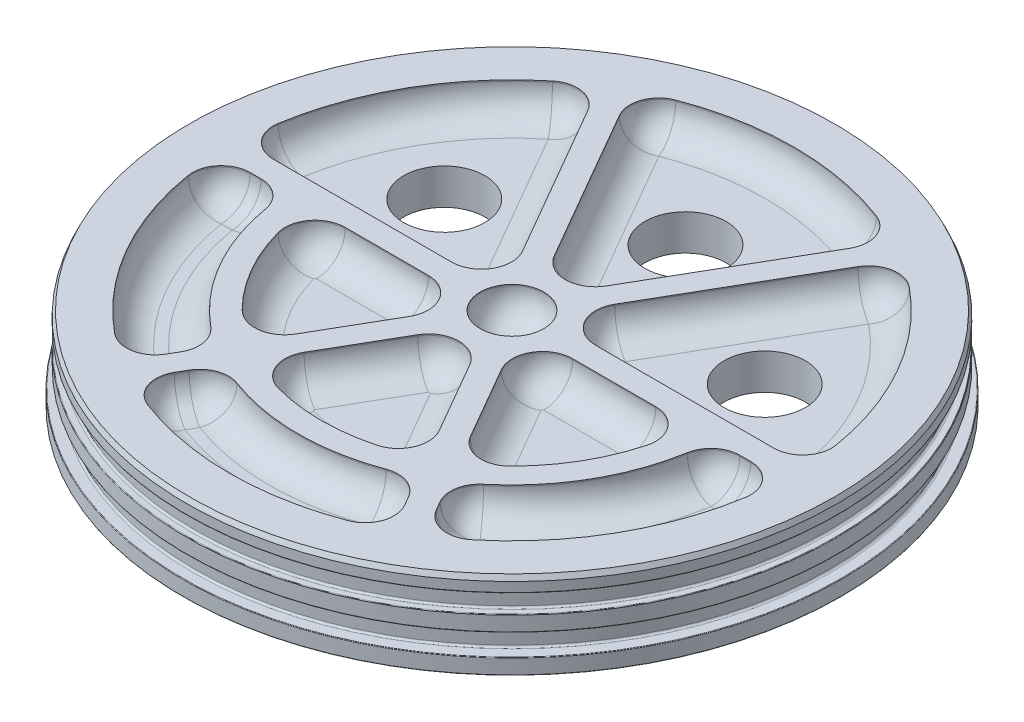
SolidWorks part; units mm, degrees
material "6061-T6 (SS)"
ref_plane "Front Plane" through (0, 0, 0) normal (0, 0, 1) x (1, 0, 0)
ref_plane "Top Plane" through (0, 0, 0) normal (0, 1, 0) x (1, 0, 0)
ref_plane "Right Plane" through (0, 0, 0) normal (1, 0, 0) x (0, 0, -1)
sketch "Sketch1" plane through (0, 0, 0) normal (0, 0, 1) x (1, 0, 0)
  line L0 (0, 48.1922) -> (0, -25.6743) construction
  line L1 (0, 0) -> (72.39, 0)
  line L2 (72.39, 0) -> (72.39, 3.429)
  line L3 (72.39, 3.429) -> (69.6468, 3.429)
  line L4 (69.6468, 3.429) -> (69.6468, 7.493)
  line L5 (69.6468, 7.493) -> (71.4248, 7.493)
  line L6 (71.4248, 7.493) -> (71.4248, 10.922)
  line L7 (71.4248, 10.922) -> (69.6468, 10.922)
  line L8 (62.0268, 18.288) -> (62.0268, 11.684)
  line L9 (62.0268, 11.684) -> (0, 11.684)
  line L10 (0, 11.684) -> (0, 0)
  line L11 (69.6468, 10.922) -> (69.6468, 14.986)
  line L12 (69.6468, 14.986) -> (71.4248, 14.986)
  line L13 (71.4248, 14.986) -> (71.4248, 18.288)
  line L14 (71.4248, 18.288) -> (62.0268, 18.288)
  dimension "D2" = 4.064
  dimension "D5" = 11.684
  dimension "D7" = 4.064
  dimension "D3" = 3.302
  dimension "D4" = 3.429
  dimension "D8" = 7.62
  dimension "D9" = 6.604
  dimension "D1" = 72.39
  dimension "D10" = 1.778
  dimension "D6" = 69.6468
revolve "Revolve1" add sketch "Sketch1" angle 360 about L0
sketch "Sketch6" plane through (0, 0, 0) normal (0, -1, 0) x (1, 0, 0)
  circle A0 centre (0, 0) radius 66.04
  dimension "D1" = 132.08
extrude "Boss-Extrude1" add sketch "Sketch6" along normal blind 2.54
fillet "CNC ID Fillet" radius 0.4064 5 edges at (-69.6468, 7.493, 0) (-69.6468, 3.429, 0) (66.04, 0, 0) (-69.6468, 14.986, 0) (-69.6468, 10.922, 0)
fillet "CNC OD Fillet" radius 0.127 6 edges at (-71.4248, 7.493, 0) (-72.39, 3.429, 0) (-71.4248, 10.922, 0) (-71.4248, 14.986, 0) (66.04, -2.54, 0) (-72.39, 0, 0)
chamfer "CNC Chamfers" distance 0.508 angle 65 1 edges at (-71.4248, 18.288, 0) first distance on face at (-62.0268, 18.288, 0)
hole_wizard "Pipe Tap Drill for 1/2 Tap - Fill Valve" positions "Sketch13" profile "Sketch14" hole size "1/2" standard "ANSI Inch" end condition through all
sketch "Sketch13" plane through (0, -2.54, 0) normal (0, -1, 0) x (-1, 0, 0)
  point P4 (0, 38.1)
  dimension "D1" = 38.1
sketch "Sketch14" plane through (0, -2.54, -38.1) normal (1, 0, 0) x (0, 0, -1)
  line L0 (0, 0) -> (0, 20.828)
  line L1 (0, 20.828) -> (8.9281, 20.828)
  line L2 (8.9281, 20.828) -> (8.9281, 0)
  line L5 (8.9281, 0) -> (0, 0)
  line L11 (0, -6.35) -> (0, 107.95) construction
  dimension "Thru Hole Dia." = 17.8562
  dimension "Thru Hole Depth" = 20.828
hole_wizard "Pipe Tap Drill for 1/4 Tap - Solenoid Valve" positions "Sketch15" profile "Sketch16" hole size "1/2" standard "ANSI Inch" end condition through all
sketch "Sketch15" plane through (0, -2.54, 0) normal (0, -1, 0) x (-1, 0, 0)
  line L2 (-35.1953, 20.32) -> (0, 0) construction
  line L4 (0, 0) -> (0, 38.1) construction
  point P4 (-35.1953, 20.32)
  dimension "D1" = 60
  dimension "D2" = 40.64
sketch "Sketch16" plane through (35.1953, -2.54, -20.32) normal (1, 0, 0) x (0, 0, -1)
  line L0 (0, 0) -> (0, 20.828)
  line L1 (0, 20.828) -> (8.9281, 20.828)
  line L2 (8.9281, 20.828) -> (8.9281, 0)
  line L5 (8.9281, 0) -> (0, 0)
  line L11 (0, -6.35) -> (0, 107.95) construction
  dimension "Thru Hole Dia." = 17.8562
  dimension "Thru Hole Depth" = 20.828
hole_wizard "Pipe Tap Drill for 1/2 Tap - Cryo Valve" positions "Sketch17" profile "Sketch18" hole size "1/2" standard "ANSI Inch" end condition through all
sketch "Sketch17" plane through (0, -2.54, 0) normal (0, -1, 0) x (-1, 0, 0)
  line L2 (35.1953, 20.32) -> (0, 0) construction
  line L5 (0, 0) -> (0, 38.1) construction
  point P4 (35.1953, 20.32)
  dimension "D1" = 60
  dimension "D2" = 40.64
sketch "Sketch18" plane through (-35.1953, -2.54, -20.32) normal (1, 0, 0) x (0, 0, -1)
  line L0 (0, 0) -> (0, 20.828)
  line L1 (0, 20.828) -> (8.9281, 20.828)
  line L2 (8.9281, 20.828) -> (8.9281, 0)
  line L5 (8.9281, 0) -> (0, 0)
  line L11 (0, -6.35) -> (0, 107.95) construction
  dimension "Thru Hole Dia." = 17.8562
  dimension "Thru Hole Depth" = 20.828
sketch "Sketch19" plane through (0, 18.288, 0) normal (0, 1, 0) x (1, 0, 0)
  line L0 (0, 0) -> (31.0134, 53.7168) construction
  line L1 (0, 0) -> (-31.0134, 53.7168) construction
  line L2 (0, 0) -> (62.0268, 0) construction
  line L3 (0, 0) -> (0, 38.1) construction
  line L4 (0, 0) -> (31.0134, -53.7168) construction
  line L5 (0, 0) -> (-31.0134, -53.7168) construction
  line L6 (0, 0) -> (-62.0268, 0) construction
  line L7 (-5.7192, 14.986) -> (-28.8137, 54.9868)
  line L8 (-15.8379, 2.54) -> (-62.0268, 2.54)
  line L9 (-10.1186, -12.446) -> (-19.2504, -28.2626)
  line L10 (5.7192, -14.986) -> (14.851, -30.8026)
  line L11 (15.8379, -2.54) -> (34.1013, -2.54)
  line L12 (10.1186, 12.446) -> (33.2131, 52.4468)
  line L13 (-10.1186, 12.446) -> (-33.2131, 52.4468)
  line L14 (-15.8379, -2.54) -> (-34.1013, -2.54)
  line L15 (-5.7192, -14.986) -> (-14.851, -30.8026)
  line L16 (10.1186, -12.446) -> (23.1162, -34.9584)
  line L17 (15.8379, 2.54) -> (62.0268, 2.54)
  line L18 (5.7192, 14.986) -> (28.8137, 54.9868)
  line L19 (0, -2.54) -> (-62.0268, -2.54) construction
  line L20 (-2.1997, 1.27) -> (-33.2131, -52.4468) construction
  line L21 (-2.1997, -1.27) -> (28.8137, -54.9868) construction
  line L22 (2.1997, -1.27) -> (-28.8137, -54.9868) construction
  line L23 (2.1997, 1.27) -> (33.2131, -52.4468) construction
  line L24 (0, -2.54) -> (62.0268, -2.54) construction
  line L25 (0, 2.54) -> (62.0268, 2.54) construction
  line L26 (2.1997, -1.27) -> (33.2131, 52.4468) construction
  line L27 (-2.1997, 1.27) -> (28.8137, 54.9868) construction
  line L28 (2.1997, 1.27) -> (-28.8137, 54.9868) construction
  line L29 (0, 2.54) -> (-62.0268, 2.54) construction
  line L30 (-2.1997, -1.27) -> (-33.2131, 52.4468) construction
  line L31 (-46.9213, -2.54) -> (-62.0268, -2.54)
  line L32 (46.9213, -2.54) -> (62.0268, -2.54)
  line L35 (-25.6604, -39.365) -> (-33.2131, -52.4468)
  line L36 (-21.2609, -41.905) -> (-28.8137, -54.9868)
  line L37 (21.2609, -41.905) -> (28.8137, -54.9868)
  line L38 (25.6604, -39.365) -> (33.2131, -52.4468)
  circle A0 centre (0, 0) radius 6.985
  circle A2 centre (0, 0) radius 62.0268
  arc A6 (-15.8379, -2.54) -> (-10.1186, -12.446) centre (-15.8379, -9.144) cw
  arc A7 (5.7192, -14.986) -> (-5.7192, -14.986) centre (0, -18.288) ccw
  arc A8 (10.1186, -12.446) -> (15.8379, -2.54) centre (15.8379, -9.144) cw
  arc A9 (15.8379, 2.54) -> (10.1186, 12.446) centre (15.8379, 9.144) cw
  arc A10 (5.7192, 14.986) -> (-5.7192, 14.986) centre (0, 18.288) cw
  arc A11 (-15.8379, 2.54) -> (-10.1186, 12.446) centre (-15.8379, 9.144) ccw
  arc A12 (-44.3774, -2.54) -> (44.3774, -2.54) centre (0, 0) ccw construction
  arc A13 (-46.9213, -2.54) -> (-25.6604, -39.365) centre (0, 0) ccw
  arc A14 (-40.48, -10.8544) -> (-29.6402, -29.6295) centre (0, 0) ccw
  arc A15 (-41.91, 0) -> (41.91, 0) centre (0, 0) ccw construction
  arc A16 (-44.45, 0) -> (44.45, 0) centre (0, 0) ccw construction
  arc A17 (-46.99, 0) -> (46.99, 0) centre (0, 0) ccw construction
  arc A19 (-10.8398, -40.4839) -> (10.8398, -40.4839) centre (0, 0) ccw
  arc A20 (23.1162, -34.9584) -> (40.48, -10.8544) centre (0, 0) ccw
  arc A21 (-21.2609, -41.905) -> (21.2609, -41.905) centre (0, 0) ccw
  arc A22 (25.6604, -39.365) -> (46.9213, -2.54) centre (0, 0) ccw
  arc A23 (-40.48, -10.8544) -> (-34.1013, -2.54) centre (-34.1013, -9.144) cw
  arc A24 (34.1013, -2.54) -> (40.48, -10.8544) centre (34.1013, -9.144) cw
  arc A25 (14.851, -30.8026) -> (10.8398, -40.4839) centre (9.1317, -34.1046) cw
  arc A26 (-10.8398, -40.4839) -> (-14.851, -30.8026) centre (-9.1317, -34.1046) cw
  arc A27 (-29.6402, -29.6295) -> (-19.2504, -28.2626) centre (-24.9696, -24.9606) ccw
  circle A28 centre (0, 0) radius 62.0268 construction
  point P12 (0, 0)
  point P13 (0, 0)
  dimension "D1" = 30
  dimension "D5" = 6.604
  dimension "D8" = 44.45
  dimension "D9" = 6.604
  dimension "D10" = 13.97
  dimension "D2" = 6
  dimension "D3" = 2.54
  dimension "D4" = 2.54
  dimension "D6" = 2.54
  dimension "D7" = 2.54
extrude "Boss-Extrude2" add sketch "Sketch19" against normal up to next contours A11 L8 L14 A6 L9 L15 A7 L10 L16 A8 L11 L17 A9 L12 L18 A10 L7 L13 region at (-0.1345, 18.288, 7.7292)
fillet "Fillet2" radius 6.35 61 edges at (-38.9063, 11.684, -2.54) (-10.1186, 11.684, -5.842) (-17.2535, 11.684, -34.9639) (0, 11.684, -11.684) (38.9063, 11.684, -2.54) (10.1186, 11.684, -5.842) (16.6174, 11.684, 23.7022) (10.1186, 11.684, 5.842) (24.9696, 11.684, 2.54) (-10.2851, 11.684, 22.8943) (0, 11.684, 11.684) (10.2851, 11.684, 22.8943) (-24.9696, 11.684, 2.54) (-10.1186, 11.684, 5.842) (-14.6845, 11.684, 20.3543) (-21.6529, 11.684, -32.4239) (17.2535, 11.684, -34.9639) (21.6529, 11.684, -32.4239) (34.0054, 11.684, 24.4965) (0, 11.684, 41.91) (-36.2951, 11.684, 20.955) (39.341, 11.684, 5.1242) (-15.2328, 11.684, 36.6324) (15.2328, 11.684, 36.6324) (-39.341, 11.684, 5.1242) (-24.1082, 11.684, 31.5082) (29.4237, 11.684, 45.8834) (40.6945, 11.684, 23.495) (54.448, 11.684, 2.54) (-25.0243, 11.684, 48.4234) (0, 11.684, 46.99) (25.0243, 11.684, 48.4234) (-54.448, 11.684, 2.54) (-40.6945, 11.684, 23.495) (-29.4237, 11.684, 45.8834) (46.9213, 14.986, 2.54) (25.6604, 14.986, 39.365) (21.2609, 14.986, 41.905) (-21.2609, 14.986, 41.905) (-25.6604, 14.986, 39.365) (-46.9213, 14.986, 2.54) (33.1871, 14.986, 52.4017) (61.9748, 14.986, 2.54) (-28.7877, 14.986, 54.9417) (28.7877, 14.986, 54.9417) (-61.9748, 14.986, 2.54) (-33.1871, 14.986, 52.4017) (-61.9748, 14.986, -2.54) (-33.1871, 14.986, -52.4017) (-28.7877, 14.986, -54.9417) (28.7877, 14.986, -54.9417) (61.9748, 14.986, -2.54) (33.1871, 14.986, -52.4017) (53.7168, 11.684, 31.0134) (0, 11.684, 62.0268) (-53.7168, 11.684, 31.0134) (-53.7168, 11.684, -31.0134) (53.7168, 11.684, -31.0134) (0, 11.684, -62.0268) (6.985, 11.684, 0) (23.1162, 14.986, 34.9584)
sketch "Sketch21" plane through (0, 18.288, 0) normal (0, 1, 0) x (1, 0, 0)
  circle A0 centre (0, 0) radius 66.3169 construction
  text T0 "                                                                                                                                                           RELEVANT EXPERIENCE"
sketch "Sketch22" plane through (0, -2.54, 0) normal (0, -1, 0) x (1, 0, 0)
  line L39 (-29.6809, -46.3289) -> (-10.1186, -12.446)
  line L59 (-15.8379, -2.54) -> (-54.9625, -2.54)
  line L74 (-29.6809, -46.3289) -> (-10.1186, -12.446)
  line L78 (-15.8379, -2.54) -> (-54.9625, -2.54)
  line L82 (-34.1013, 2.54) -> (-15.8379, 2.54)
  line L86 (-10.1186, 12.446) -> (-19.2504, 28.2626)
  line L90 (-34.1013, 2.54) -> (-15.8379, 2.54)
  line L94 (-10.1186, 12.446) -> (-19.2504, 28.2626)
  line L98 (15.8379, 2.54) -> (34.1013, 2.54)
  line L101 (19.4151, 28.548) -> (10.1186, 12.446)
  line L102 (15.8379, 2.54) -> (34.1013, 2.54)
  line L103 (19.4151, 28.548) -> (10.1186, 12.446)
  line L104 (-14.851, 30.8026) -> (-5.7192, 14.986)
  line L105 (5.7192, 14.986) -> (14.851, 30.8026)
  line L106 (-14.851, 30.8026) -> (-5.7192, 14.986)
  line L107 (5.7192, 14.986) -> (14.851, 30.8026)
  line L108 (-28.4967, 44.2777) -> (-29.6809, 46.3289)
  line L109 (-54.9625, 2.54) -> (-52.5939, 2.54)
  line L110 (-28.4967, 44.2777) -> (-29.6809, 46.3289)
  line L111 (-54.9625, 2.54) -> (-52.5939, 2.54)
  line L112 (24.0973, 46.8177) -> (25.2815, 48.8689)
  line L113 (-25.2815, 48.8689) -> (-24.0973, 46.8177)
  line L114 (24.0973, 46.8177) -> (25.2815, 48.8689)
  line L115 (-25.2815, 48.8689) -> (-24.0973, 46.8177)
  line L116 (52.5939, 2.54) -> (54.9625, 2.54)
  line L117 (29.6809, 46.3289) -> (28.4967, 44.2777)
  line L118 (52.5939, 2.54) -> (54.9625, 2.54)
  line L119 (29.6809, 46.3289) -> (28.4967, 44.2777)
  line L120 (10.1186, -12.446) -> (29.6809, -46.3289)
  line L121 (54.9625, -2.54) -> (15.8379, -2.54)
  line L122 (10.1186, -12.446) -> (29.6809, -46.3289)
  line L123 (54.9625, -2.54) -> (15.8379, -2.54)
  line L124 (-5.7192, -14.986) -> (-25.2815, -48.8689)
  line L125 (25.2815, -48.8689) -> (5.7192, -14.986)
  line L126 (-5.7192, -14.986) -> (-25.2815, -48.8689)
  line L127 (25.2815, -48.8689) -> (5.7192, -14.986)
  circle A3 centre (0, 0) radius 6.985
  circle A93 centre (0, 0) radius 6.985
  arc A205 (-61.231, -9.9039) -> (-39.1925, -48.0757) centre (0, 0) ccw
  arc A214 (-39.1925, -48.0757) -> (-29.6809, -46.3289) centre (-35.1802, -43.1539) ccw
  arc A217 (-10.1186, -12.446) -> (-15.8379, -2.54) centre (-15.8379, -9.144) ccw
  arc A229 (-54.9625, -2.54) -> (-61.231, -9.9039) centre (-54.9625, -8.89) ccw
  arc A241 (-61.231, -9.9039) -> (-39.1925, -48.0757) centre (0, 0) ccw
  arc A267 (-39.1925, -48.0757) -> (-29.6809, -46.3289) centre (-35.1802, -43.1539) ccw
  arc A268 (-10.1186, -12.446) -> (-15.8379, -2.54) centre (-15.8379, -9.144) ccw
  arc A269 (-54.9625, -2.54) -> (-61.231, -9.9039) centre (-54.9625, -8.89) ccw
  arc A270 (-19.2504, 28.2626) -> (-29.6402, 29.6295) centre (-24.9696, 24.9606) ccw
  arc A271 (-29.6402, 29.6295) -> (-40.48, 10.8544) centre (0, 0) ccw
  arc A272 (-40.48, 10.8544) -> (-34.1013, 2.54) centre (-34.1013, 9.144) ccw
  arc A273 (-15.8379, 2.54) -> (-10.1186, 12.446) centre (-15.8379, 9.144) ccw
  arc A274 (-19.2504, 28.2626) -> (-29.6402, 29.6295) centre (-24.9696, 24.9606) ccw
  arc A275 (-29.6402, 29.6295) -> (-40.48, 10.8544) centre (0, 0) ccw
  arc A276 (-40.48, 10.8544) -> (-34.1013, 2.54) centre (-34.1013, 9.144) ccw
  arc A277 (-15.8379, 2.54) -> (-10.1186, 12.446) centre (-15.8379, 9.144) ccw
  arc A278 (34.1013, 2.54) -> (40.48, 10.8544) centre (34.1013, 9.144) ccw
  arc A279 (40.48, 10.8544) -> (29.3634, 29.9039) centre (0, 0) ccw
  arc A280 (29.3634, 29.9039) -> (19.4151, 28.548) centre (24.9144, 25.373) ccw
  arc A281 (10.1186, 12.446) -> (15.8379, 2.54) centre (15.8379, 9.144) ccw
  arc A282 (34.1013, 2.54) -> (40.48, 10.8544) centre (34.1013, 9.144) ccw
  arc A283 (40.48, 10.8544) -> (29.3634, 29.9039) centre (0, 0) ccw
  arc A284 (29.3634, 29.9039) -> (19.4151, 28.548) centre (24.9144, 25.373) ccw
  arc A285 (10.1186, 12.446) -> (15.8379, 2.54) centre (15.8379, 9.144) ccw
  arc A286 (10.8398, 40.4839) -> (-10.8398, 40.4839) centre (0, 0) ccw
  arc A287 (-10.8398, 40.4839) -> (-14.851, 30.8026) centre (-9.1317, 34.1046) ccw
  arc A288 (-5.7192, 14.986) -> (5.7192, 14.986) centre (0, 18.288) ccw
  arc A289 (14.851, 30.8026) -> (10.8398, 40.4839) centre (9.1317, 34.1046) ccw
  arc A290 (10.8398, 40.4839) -> (-10.8398, 40.4839) centre (0, 0) ccw
  arc A291 (-10.8398, 40.4839) -> (-14.851, 30.8026) centre (-9.1317, 34.1046) ccw
  arc A292 (-5.7192, 14.986) -> (5.7192, 14.986) centre (0, 18.288) ccw
  arc A293 (14.851, 30.8026) -> (10.8398, 40.4839) centre (9.1317, 34.1046) ccw
  arc A296 (29.6809, -46.3289) -> (39.1925, -48.0757) centre (35.1802, -43.1539) ccw
  arc A297 (39.1925, -48.0757) -> (61.231, -9.9039) centre (0, 0) ccw
  arc A298 (-29.9488, 36.2095) -> (-46.3328, 7.8317) centre (0, 0) ccw
  arc A299 (-29.9488, 36.2095) -> (-28.4967, 44.2777) centre (-33.9959, 41.1027) ccw
  arc A300 (-29.6809, 46.3289) -> (-39.1925, 48.0757) centre (-35.1802, 43.1539) ccw
  arc A301 (-39.1925, 48.0757) -> (-61.231, 9.9039) centre (0, 0) ccw
  arc A302 (-61.231, 9.9039) -> (-54.9625, 2.54) centre (-54.9625, 8.89) ccw
  arc A303 (-52.5939, 2.54) -> (-46.3328, 7.8317) centre (-52.5939, 8.89) ccw
  arc A304 (-29.9488, 36.2095) -> (-46.3328, 7.8317) centre (0, 0) ccw
  arc A305 (-29.9488, 36.2095) -> (-28.4967, 44.2777) centre (-33.9959, 41.1027) ccw
  arc A306 (-29.6809, 46.3289) -> (-39.1925, 48.0757) centre (-35.1802, 43.1539) ccw
  arc A307 (-39.1925, 48.0757) -> (-61.231, 9.9039) centre (0, 0) ccw
  arc A308 (-61.231, 9.9039) -> (-54.9625, 2.54) centre (-54.9625, 8.89) ccw
  arc A309 (-52.5939, 2.54) -> (-46.3328, 7.8317) centre (-52.5939, 8.89) ccw
  arc A310 (16.384, 44.0412) -> (-16.384, 44.0412) centre (0, 0) ccw
  arc A311 (16.384, 44.0412) -> (24.0973, 46.8177) centre (18.598, 49.9927) ccw
  arc A312 (25.2815, 48.8689) -> (22.0385, 57.9796) centre (19.7823, 52.0439) ccw
  arc A313 (22.0385, 57.9796) -> (-22.0385, 57.9796) centre (0, 0) ccw
  arc A314 (-22.0385, 57.9796) -> (-25.2815, 48.8689) centre (-19.7823, 52.0439) ccw
  arc A315 (-24.0973, 46.8177) -> (-16.384, 44.0412) centre (-18.598, 49.9927) ccw
  arc A316 (16.384, 44.0412) -> (-16.384, 44.0412) centre (0, 0) ccw
  arc A317 (16.384, 44.0412) -> (24.0973, 46.8177) centre (18.598, 49.9927) ccw
  arc A318 (25.2815, 48.8689) -> (22.0385, 57.9796) centre (19.7823, 52.0439) ccw
  arc A319 (22.0385, 57.9796) -> (-22.0385, 57.9796) centre (0, 0) ccw
  arc A320 (-22.0385, 57.9796) -> (-25.2815, 48.8689) centre (-19.7823, 52.0439) ccw
  arc A321 (-24.0973, 46.8177) -> (-16.384, 44.0412) centre (-18.598, 49.9927) ccw
  arc A322 (46.3328, 7.8317) -> (29.9488, 36.2095) centre (0, 0) ccw
  arc A323 (46.3328, 7.8317) -> (52.5939, 2.54) centre (52.5939, 8.89) ccw
  arc A324 (54.9625, 2.54) -> (61.231, 9.9039) centre (54.9625, 8.89) ccw
  arc A325 (61.231, 9.9039) -> (39.1925, 48.0757) centre (0, 0) ccw
  arc A326 (39.1925, 48.0757) -> (29.6809, 46.3289) centre (35.1802, 43.1539) ccw
  arc A327 (28.4967, 44.2777) -> (29.9488, 36.2095) centre (33.9959, 41.1027) ccw
  arc A328 (46.3328, 7.8317) -> (29.9488, 36.2095) centre (0, 0) ccw
  arc A329 (46.3328, 7.8317) -> (52.5939, 2.54) centre (52.5939, 8.89) ccw
  arc A330 (54.9625, 2.54) -> (61.231, 9.9039) centre (54.9625, 8.89) ccw
  arc A331 (61.231, 9.9039) -> (39.1925, 48.0757) centre (0, 0) ccw
  arc A332 (39.1925, 48.0757) -> (29.6809, 46.3289) centre (35.1802, 43.1539) ccw
  arc A333 (28.4967, 44.2777) -> (29.9488, 36.2095) centre (33.9959, 41.1027) ccw
  arc A334 (61.231, -9.9039) -> (54.9625, -2.54) centre (54.9625, -8.89) ccw
  arc A335 (15.8379, -2.54) -> (10.1186, -12.446) centre (15.8379, -9.144) ccw
  arc A336 (29.6809, -46.3289) -> (39.1925, -48.0757) centre (35.1802, -43.1539) ccw
  arc A337 (39.1925, -48.0757) -> (61.231, -9.9039) centre (0, 0) ccw
  arc A338 (61.231, -9.9039) -> (54.9625, -2.54) centre (54.9625, -8.89) ccw
  arc A339 (15.8379, -2.54) -> (10.1186, -12.446) centre (15.8379, -9.144) ccw
  arc A340 (-25.2815, -48.8689) -> (-22.0385, -57.9796) centre (-19.7823, -52.0439) ccw
  arc A341 (-22.0385, -57.9796) -> (22.0385, -57.9796) centre (0, 0) ccw
  arc A342 (22.0385, -57.9796) -> (25.2815, -48.8689) centre (19.7823, -52.0439) ccw
  arc A343 (5.7192, -14.986) -> (-5.7192, -14.986) centre (0, -18.288) ccw
  arc A344 (-25.2815, -48.8689) -> (-22.0385, -57.9796) centre (-19.7823, -52.0439) ccw
  arc A345 (-22.0385, -57.9796) -> (22.0385, -57.9796) centre (0, 0) ccw
  arc A346 (22.0385, -57.9796) -> (25.2815, -48.8689) centre (19.7823, -52.0439) ccw
  arc A347 (5.7192, -14.986) -> (-5.7192, -14.986) centre (0, -18.288) ccw
  circle M63 centre (-35.1953, -20.32) radius 8.9281
  circle M64 centre (35.1953, -20.32) radius 8.9281
  circle M65 centre (0, -38.1) radius 8.9281
  dimension "D1" = 0
  dimension "D2" = 0
  dimension "D3" = 0
  dimension "D4" = 0
  dimension "D5" = 0
  dimension "D6" = 0
  dimension "D7" = 0
  dimension "D8" = 0
  dimension "D9" = 0
  dimension "D10" = 0
extrude "Cut-Extrude1" cut sketch "Sketch22" against normal blind 6.35 contours M64 | M65 | M63 | A93 | L102 A282 A283 A284 L103 A285 | A290 A291 L106 A292 L107 A293 | A274 A275 A276 L90 A277 L94 | A304 A309 L111 A308 A307 A306 L110 A305 | A316 A321 L115 A320 A319 A318 L114 A317 | A328 A333 L119 A332 A331 A330 L118 A329 region at (-34.1599, -2.54, -48.7097) region at (10.726, -2.54, -6.1926) region at (0, -2.54, -12.4097)
fillet "Fillet3" radius 6.35 61 edges at (59.7978, 3.81, -4.7739) (53.7168, 3.81, -31.0134) (34.0332, 3.81, -49.3995) (19.8998, 3.81, -29.3875) (10.1186, 3.81, -5.842) (-10.1186, 3.81, -5.842) (-19.8998, 3.81, -29.3875) (-34.0332, 3.81, -49.3995) (-53.7168, 3.81, -31.0134) (-59.7978, 3.81, -4.7739) (0, 3.81, -11.684) (15.5004, 3.81, -31.9275) (25.7646, 3.81, -54.1734) (0, 3.81, -62.0268) (-25.7646, 3.81, -54.1734) (-40.6945, 3.81, 23.495) (-48.495, 3.81, 4.0401) (-53.7782, 3.81, 2.54) (-59.7978, 3.81, 4.7739) (-53.7168, 3.81, 31.0134) (-34.0332, 3.81, 49.3995) (-29.0888, 3.81, 45.3033) (-27.7464, 3.81, 39.9779) (0, 3.81, 46.99) (-20.7487, 3.81, 44.018) (-24.6894, 3.81, 47.8433) (-25.7646, 3.81, 54.1734) (0, 3.81, 62.0268) (25.7646, 3.81, 54.1734) (24.6894, 3.81, 47.8433) (20.7487, 3.81, 44.018) (40.6945, 3.81, 23.495) (27.7464, 3.81, 39.9779) (29.0888, 3.81, 45.3033) (34.0332, 3.81, 49.3995) (53.7168, 3.81, 31.0134) (59.7978, 3.81, 4.7739) (53.7782, 3.81, 2.54) (48.495, 3.81, 4.0401) (14.7669, 3.81, 20.497) (24.0568, 3.81, 31.6648) (36.1973, 3.81, 21.1235) (39.341, 3.81, 5.1242) (24.9696, 3.81, 2.54) (10.1186, 3.81, 5.842) (10.2851, 3.81, 22.8943) (0, 3.81, 11.684) (-10.2851, 3.81, 22.8943) (-15.2328, 3.81, 36.6324) (0, 3.81, 41.91) (15.2328, 3.81, 36.6324) (-10.1186, 3.81, 5.842) (-24.9696, 3.81, 2.54) (-39.341, 3.81, 5.1242) (-36.2951, 3.81, 20.955) (-24.1082, 3.81, 31.5082) (-14.6845, 3.81, 20.3543) (6.985, 3.81, 0) (35.4002, 3.81, -2.54) (-35.4002, 3.81, -2.54) (-15.5004, 3.81, -31.9275)
sketch "Sketch20" plane through (0, 3.81, 0) normal (0, -1, 0) x (-1, 0, 0)
  line L0 (0, 0) -> (-35.1953, 20.32) construction
  line L1 (-40.2753, 11.5212) -> (-30.1153, 29.1188) construction
  line L2 (-11.43, 38.1) -> (11.43, 38.1) construction
  line L3 (0, 0) -> (0, 38.1) construction
  line L4 (40.2753, 11.5212) -> (30.1153, 29.1188) construction
  line L5 (0, 0) -> (35.1953, 20.32) construction
  arc A1 (11.43, 38.1) -> (-11.43, 38.1) centre (0, 38.1) ccw construction
  arc A2 (11.43, 38.1) -> (-11.43, 38.1) centre (0, 38.1) cw construction
  arc A3 (-40.2753, 11.5212) -> (-30.1153, 29.1188) centre (-35.1953, 20.32) ccw construction
  arc A4 (-40.2753, 11.5212) -> (-30.1153, 29.1188) centre (-35.1953, 20.32) cw construction
  arc A5 (40.2753, 11.5212) -> (30.1153, 29.1188) centre (35.1953, 20.32) ccw construction
  arc A6 (40.2753, 11.5212) -> (30.1153, 29.1188) centre (35.1953, 20.32) cw construction
  text T1 "FILL" font "Century Gothic" height in points 20
  text T3 "INJECTOR" font "Century Gothic" height in points 12
  text T4 "DUMP" font "Century Gothic" height in points 14
  point P14 (-35.1953, 20.32)
  dimension "D1" = 11.43
  dimension "D2" = 10.16
sketch "Sketch24" plane through (0, -2.54, 0) normal (0, -1, 0) x (1, 0, 0)
  arc A0 (-42.672, 0) -> (42.672, 0) centre (0, 0) cw construction
  text T0 "THIS SIDE OUT" font "Century Gothic" height in points 12
  dimension "D1" = 42.672
equation "\"D6@Sketch1\"=5.484/2"
equation "\"D1@Sketch1\"=5.7/2"
